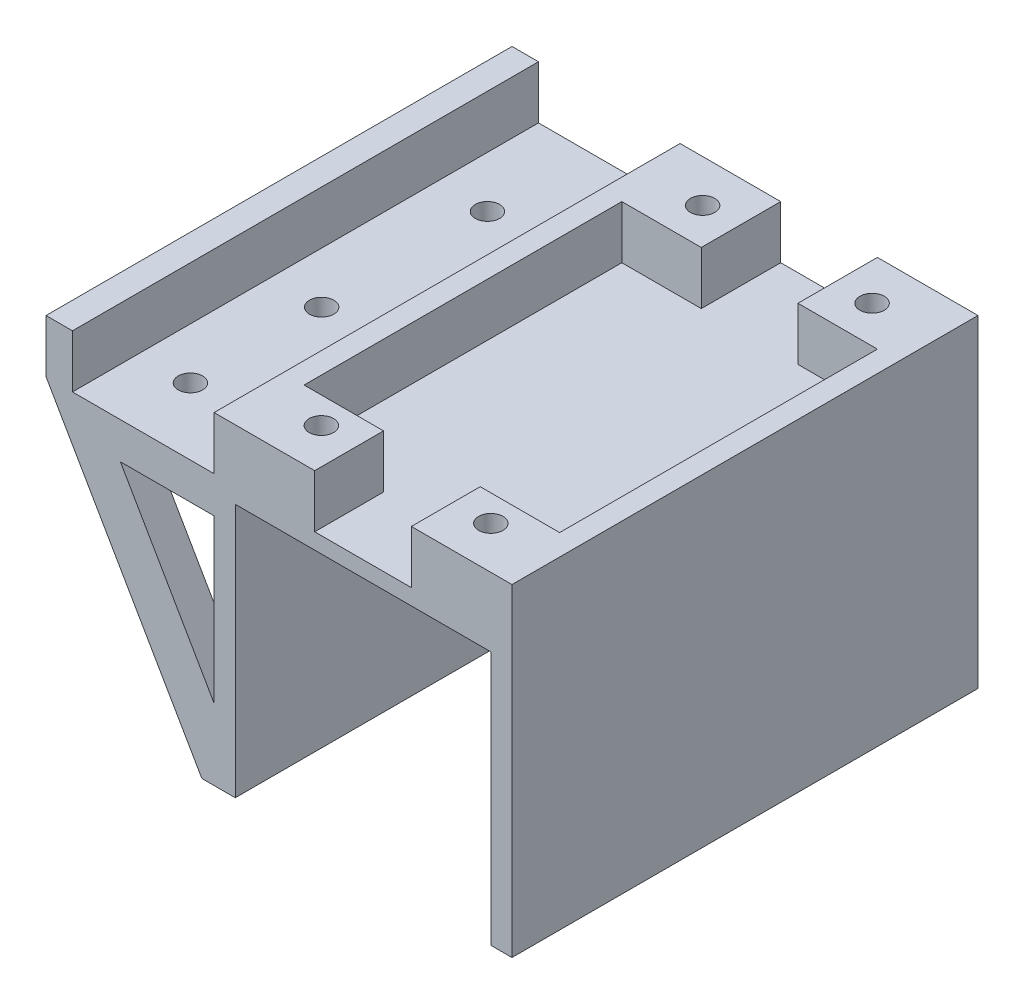
SolidWorks part; units mm, degrees
ref_plane "Front" through (0, 0, 0) normal (0, 0, 1) x (1, 0, 0)
ref_plane "Top" through (0, 0, 0) normal (0, 1, 0) x (1, 0, 0)
ref_plane "Right" through (0, 0, 0) normal (1, 0, 0) x (0, 0, -1)
sketch "Sketch1" plane through (0, 0, 0) normal (0, 0, 1) x (1, 0, 0)
  line L0 (0, 0) -> (0, 70)
  line L1 (0, 70) -> (56.254, 70)
  line L2 (56.254, 70) -> (56.254, 0)
  line L3 (56.254, 0) -> (52.254, 0)
  line L4 (52.254, 0) -> (52.254, 65)
  line L5 (52.254, 65) -> (4, 65)
  line L6 (4, 65) -> (4, 0)
  line L7 (4, 0) -> (0, 0)
  line L9 (4, 55) -> (52.254, 55)
  line L10 (4, 55) -> (4, 52)
  line L11 (4, 52) -> (52.254, 52)
  line L12 (52.254, 55) -> (52.254, 52)
  dimension "D1" = 48.254
  dimension "D2" = 4
  dimension "D3" = 4
  dimension "D4" = 5
  dimension "D5" = 70
  dimension "D6" = 3
  dimension "D7" = 10
extrude "Boss-Extrude1" add sketch "Sketch1" along normal blind 70 contours L7 L6 L5 L4 L3 L2 L1 L0 | L9 L12 L11 L10 region at (0.898, 35, 0)
sketch "Sketch3" plane through (0, 0, 70) normal (0, 0, 1) x (1, 0, 0)
  line L0 (0, 70) -> (-40.3946, 70)
  line L1 (-40.3946, 70) -> (0, 0.0344)
  line L2 (0, 0) -> (0, 70) construction
  line L3 (0, 0.0344) -> (0, 70)
  line L4 (0, 70) -> (0, 62.5)
  line L5 (0, 62.5) -> (-26, 62.5)
  line L6 (-26, 62.5) -> (0, 17.4667)
  line L7 (0, 17.4667) -> (0, 0.0344)
  line M11 (0, 70) -> (0, 0)
  dimension "D1" = 60
  dimension "D2" = 180
  dimension "D3" = 7.5
  dimension "D4" = 26
extrude "Boss-Extrude3" add sketch "Sketch3" against normal blind 8 contours L6 L5 L0 L1 M11 region at (-16.8587, 46.1047, 70)
sketch "Sketch4" plane through (0, 0, 0) normal (0, 0, -1) x (-1, 0, 0)
  line L0 (0, 70) -> (40.3946, 70)
  line L1 (40.3946, 70) -> (0, 0)
  line L2 (0, 0) -> (0, 17.4667)
  line L3 (0, 17.4667) -> (26, 62.5)
  line L4 (26, 62.5) -> (0, 62.5)
  line L5 (0, 62.5) -> (0, 70)
extrude "Boss-Extrude4" add sketch "Sketch4" against normal blind 8
ref_plane "Plane1" through (0, 0, 39) normal (0, 0, -1) x (-1, 0, 0)
sketch "Sketch5" plane through (0, 0, 39) normal (0, 0, -1) x (-1, 0, 0)
  line L0 (0, 62.5) -> (0, 70)
  line L1 (0, 70) -> (40.3946, 70)
  line L2 (40.3946, 70) -> (0, 0)
  line L3 (0, 0) -> (0, 17.4667)
  line L4 (0, 17.4667) -> (26, 62.5)
  line L5 (26, 62.5) -> (0, 62.5)
extrude "Boss-Extrude5" add sketch "Sketch5" along normal blind 8
sketch "Sketch6" plane through (0, 0, 0) normal (0, 0, -1) x (-1, 0, 0)
  line L5 (0, 62.5) -> (36.0666, 62.5)
  line L6 (0, 0) -> (40.3946, 70) construction
  line L7 (36.0666, 62.5) -> (40.3946, 70)
  line L8 (40.3946, 70) -> (0, 70)
  line L9 (40.3946, 70) -> (-56.254, 70) construction
  line L10 (0, 70) -> (0, 62.5)
  line L11 (-4, 0) -> (0, 0)
  line L12 (0, 0) -> (7.5019, 13)
  line L13 (7.5019, 13) -> (-4, 13)
  line L14 (-4, 52) -> (-4, 0) construction
  line L15 (-4, 13) -> (-4, 0)
  dimension "D1" = 13
extrude "Boss-Extrude6" add sketch "Sketch6" against normal blind 70
sketch "Sketch7" plane through (0, 0, 70) normal (0, 0, 1) x (1, 0, 0)
  line L0 (0, 17.4667) -> (0, 62.5) construction
  line L1 (-40.3946, 70) -> (0, 70)
  line L2 (-40.3946, 70) -> (-40.3946, 53)
  line L3 (-40.3946, 53) -> (0, 53)
  line L4 (0, 70) -> (0, 53)
  dimension "D1" = 17
extrude "Cut-Extrude3" cut sketch "Sketch7" against normal blind 70
sketch "Sketch8" plane through (0, 0, 0) normal (0, 0, -1) x (-1, 0, 0)
  line L1 (-4, 55) -> (-4, 52)
  line L2 (-4, 52) -> (-52.254, 52) construction
  line L3 (-4, 52) -> (30.0074, 52)
  line L4 (0, 0) -> (30.5845, 53) construction
  line L6 (30.0074, 52) -> (31.7386, 55)
  line L7 (31.7386, 55) -> (-4, 55)
  dimension "D1" = 180
extrude "Boss-Extrude7" add sketch "Sketch8" against normal blind 70
sketch "Sketch11" plane through (0, 0, 70) normal (0, 0, 1) x (1, 0, 0)
  line L0 (-31.7386, 55) -> (0, 0)
  line L3 (-31.7386, 55) -> (0, 55) construction
  line L4 (-27.289, 55) -> (-31.7386, 55)
  line L5 (-27.289, 55) -> (-3.0537, 13)
  line L6 (-3.0537, 13) -> (0, 0)
extrude "Boss-Extrude10" add sketch "Sketch11" against normal blind 8
sketch "Sketch12" plane through (0, 0, 70) normal (0, 0, 1) x (1, 0, 0)
  line L0 (-31.7386, 55) -> (-27.7598, 48.1051)
  line L1 (0, 0) -> (-31.7386, 55) construction
  line L2 (-27.7598, 48.1051) -> (0, 48.1051)
  line L3 (0, 17.4667) -> (0, 52) construction
  line L4 (0, 48.1051) -> (0, 55)
  line L5 (0, 55) -> (-31.7386, 55)
extrude "Boss-Extrude11" add sketch "Sketch12" against normal blind 70
sketch "Sketch13" plane through (0, 0, 0) normal (0, -1, 0) x (1, 0, 0)
  line L1 (67.4394, -10.6205) -> (-15.562, -10.6205)
  line L2 (67.4394, -10.6205) -> (67.4394, 77.2481)
  line L3 (67.4394, 77.2481) -> (-15.562, 77.2481)
  line L4 (-15.562, -10.6205) -> (-15.562, 77.2481)
extrude "Cut-Extrude4" cut sketch "Sketch13" against normal blind 4
sketch "Sketch14" plane through (0, 0, 70) normal (0, 0, 1) x (1, 0, 0)
  line L0 (-2.3083, 4) -> (-31.7386, 55)
  line L1 (-31.7386, 55) -> (0, 55)
  line L2 (0, 55) -> (0, 70)
  line L3 (0, 70) -> (56.254, 70)
  line L4 (56.254, 70) -> (56.254, 4)
  line L5 (56.254, 4) -> (52.254, 4)
  line L6 (52.254, 4) -> (52.254, 52)
  line L7 (52.254, 52) -> (4, 52)
  line L8 (4, 52) -> (4, 4)
  line L9 (4, 4) -> (-2.3083, 4)
  line L14 (-17.6891, 48.1051) -> (0, 48.1051)
  line L15 (52.254, 55) -> (4, 55)
  line L16 (52.254, 55) -> (52.254, 65)
  line L17 (52.254, 65) -> (4, 65)
  line L18 (4, 55) -> (4, 65)
  line L19 (-17.6891, 48.1051) -> (0, 48.1051) construction
  line L20 (0, 48.1051) -> (0, 17.4667)
  line L21 (0, 17.4667) -> (-17.6891, 48.1051)
extrude "Boss-Extrude12" add sketch "Sketch14" along normal blind 20
sketch "Sketch15" plane through (0, 0, 90) normal (0, 0, 1) x (1, 0, 0)
  line L0 (56.254, 4) -> (56.254, 70) construction
  line L1 (56.254, 65) -> (37.264, 65)
  line L2 (56.254, 65) -> (56.254, 55)
  line L3 (56.254, 55) -> (37.264, 55)
  line L4 (37.264, 65) -> (37.264, 55)
  line L5 (4, 55) -> (52.254, 55) construction
  dimension "D1" = 18.99
sketch "Sketch16" plane through (0, 0, 90) normal (0, 0, 1) x (1, 0, 0)
  line L1 (0, 70) -> (56.254, 70)
  line L2 (0, 70) -> (0, 65)
  line L3 (0, 65) -> (56.254, 65)
  line L4 (56.254, 70) -> (56.254, 65)
extrude "Cut-Extrude5" cut sketch "Sketch16" against normal blind 100
sketch "Sketch17" plane through (0, 65, 0) normal (0, 1, 0) x (1, 0, 0)
  line L1 (52.254, 0) -> (37.254, 0)
  line L2 (52.254, 0) -> (52.254, -15)
  line L3 (52.254, -15) -> (37.254, -15)
  line L4 (37.254, 0) -> (37.254, -15)
  line L5 (52.254, -90) -> (37.254, -90)
  line L6 (52.254, -90) -> (52.254, -75)
  line L7 (52.254, -75) -> (37.254, -75)
  line L8 (37.254, -90) -> (37.254, -75)
  dimension "D1" = 15
  dimension "D2" = 15
  dimension "D3" = 15
  dimension "D4" = 15
extrude "Boss-Extrude14" add sketch "Sketch17" against normal blind 13
sketch "Sketch21" plane through (0, 52, 0) normal (0, -1, 0) x (-1, 0, 0)
  circle A0 centre (-44.254, -80) radius 2.3
  circle A1 centre (-44.254, -8) radius 2.3
sketch "Sketch22" plane through (0, 52, 0) normal (0, -1, 0) x (1, 0, 0)
  line L1 (48.0965, 6.0036) -> (47.9041, 10.3295)
  line L2 (47.9041, 10.3295) -> (44.0617, 12.3259)
  line L3 (44.0617, 12.3259) -> (40.4115, 9.9964)
  line L4 (40.4115, 9.9964) -> (40.6039, 5.6705)
  line L5 (40.6039, 5.6705) -> (44.4463, 3.6741)
  line L6 (44.4463, 3.6741) -> (48.0965, 6.0036)
  line L7 (45.2007, 75.7746) -> (48.3866, 78.7072)
  line L8 (48.3866, 78.7072) -> (47.4399, 82.9325)
  line L9 (47.4399, 82.9325) -> (43.3073, 84.2254)
  line L10 (43.3073, 84.2254) -> (40.1214, 81.2928)
  line L11 (40.1214, 81.2928) -> (41.0681, 77.0675)
  line L12 (41.0681, 77.0675) -> (45.2007, 75.7746)
  circle A0 centre (44.254, 8) radius 3.75 construction
  circle A1 centre (44.254, 80) radius 3.75 construction
  point P10 (42.2366, 11.1611)
  dimension "D1" = 7.5
  dimension "D2" = 7.5
extrude "Cut-Extrude8" cut sketch "Sketch22" against normal blind 5
extrude "Cut-Extrude9" cut sketch "Sketch21" against normal blind 15
sketch "Sketch23" plane through (0, 0, 0) normal (-0.8661, -0.4998, 0) x (0, 0, 1)
  line L0 (90, 63.5007) -> (90, 4.6182) construction
  line L1 (70, 55.5401) -> (82, 55.5401)
  line L2 (70, 55.5401) -> (70, 15.0093)
  line L3 (70, 15.0093) -> (82, 15.0093)
  line L4 (82, 55.5401) -> (82, 15.0093)
  line L5 (62, 55.5401) -> (62, 15.0093) construction
  dimension "D1" = 8
  dimension "D2" = 8
extrude "Cut-Extrude10" cut sketch "Sketch23" against normal blind 9
sketch "Sketch25" plane through (0, 48.1051, 0) normal (0, -1, 0) x (-1, 0, 0)
  circle A0 centre (17.0755, -19.3006) radius 2.3
  circle A1 centre (17.0755, -50.6137) radius 2.3
extrude "Cut-Extrude11" cut sketch "Sketch25" against normal blind 20
sketch "Sketch26" plane through (0, 48.1051, 0) normal (0, -1, 0) x (1, 0, 0)
  circle A0 centre (-17.0755, 75.3913) radius 2.3
extrude "Cut-Extrude12" cut sketch "Sketch26" against normal blind 20
sketch "Sketch27" plane through (0, 0, 90) normal (0, 0, 1) x (1, 0, 0)
  line L0 (-23.3104, 48.1051) -> (-27.7598, 48.1051)
  line L1 (-31.7386, 55) -> (-2.3083, 4) construction
  line L2 (-27.7598, 48.1051) -> (-31.7386, 55)
  line L3 (-31.7386, 55) -> (-23.3104, 55)
  line L4 (0, 55) -> (-31.7386, 55) construction
  line L5 (-23.3104, 55) -> (-23.3104, 48.1051)
extrude "Boss-Extrude16" add sketch "Sketch27" against normal blind 20
sketch "Sketch28" plane through (0, 55, 0) normal (0, 1, 0) x (1, 0, 0)
  line L0 (4, -90) -> (37.254, -90) construction
  line L1 (4, 0) -> (19, 0)
  line L2 (4, 0) -> (4, -15)
  line L3 (4, -15) -> (19, -15)
  line L4 (19, 0) -> (19, -15)
  line L5 (4, -90) -> (19, -90)
  line L6 (4, -90) -> (4, -75)
  line L7 (4, -75) -> (19, -75)
  line L8 (19, -90) -> (19, -75)
  line L9 (4, 0) -> (4, -90) construction
  dimension "D1" = 15
  dimension "D2" = 15
  dimension "D3" = 15
  dimension "D4" = 15
extrude "Boss-Extrude17" add sketch "Sketch28" along normal blind 10
sketch "Sketch29" plane through (0, 52, 0) normal (0, -1, 0) x (-1, 0, 0)
  circle A0 centre (-12.254, -8) radius 2.3
  circle A1 centre (-12.254, -80) radius 2.3
extrude "Cut-Extrude13" cut sketch "Sketch29" against normal blind 20
sketch "Sketch30" plane through (0, 48.1051, 0) normal (0, -1, 0) x (1, 0, 0)
  line L1 (-27.7598, 70) -> (-17.3688, 70)
  line L2 (-27.7598, 70) -> (-27.7598, 82)
  line L3 (-27.7598, 82) -> (-17.3688, 82)
  line L4 (-17.3688, 70) -> (-17.3688, 82)
extrude "Boss-Extrude18" add sketch "Sketch30" against normal blind 5
sketch "Sketch31" plane through (0, 48.1051, 0) normal (0, -1, 0) x (1, 0, 0)
  circle A0 centre (-17.0755, 75.3913) radius 2.3
extrude "Cut-Extrude14" cut sketch "Sketch31" against normal blind 45
sketch "Sketch33" plane through (0, 55, 0) normal (0, 1, 0) x (1, 0, 0)
  circle A0 centre (27.6164, -46.5233) radius 1
  circle A1 centre (26.8974, -20.9206) radius 1
  circle A2 centre (28.9102, -66.6327) radius 1
  circle A3 centre (-20.9687, -5.2719) radius 1
  circle A4 centre (-23.4497, -23.5026) radius 1
  circle A5 centre (-17.8546, -42.0102) radius 1
  circle A6 centre (-22.4497, -64.7625) radius 1
  circle A7 centre (-17.8546, -85.6157) radius 1
ref_plane "Plane2" through (-31.7386, 55, 90) normal (0.4998, -0.8661, 0) x (-0.8661, -0.4998, 0)
sketch "Sketch36" plane through (0, 0, 90) normal (0, 0, 1) x (1, 0, 0)
  circle A0 centre (23.0361, 36.9328) radius 60.0365
extrude "Cut-Extrude15" cut sketch "Sketch36" against normal blind 2
sketch "Sketch37" plane through (0, 55, 0) normal (0, 1, 0) x (1, 0, 0)
  line L0 (-31.7386, -88) -> (0, -88) construction
  line L1 (-31.7386, 0) -> (-26.7386, 0)
  line L2 (-31.7386, 0) -> (-31.7386, -88)
  line L3 (-31.7386, -88) -> (-26.7386, -88)
  line L4 (-26.7386, 0) -> (-26.7386, -88)
  dimension "D1" = 5
extrude "Boss-Extrude19" add sketch "Sketch37" along normal blind 10
